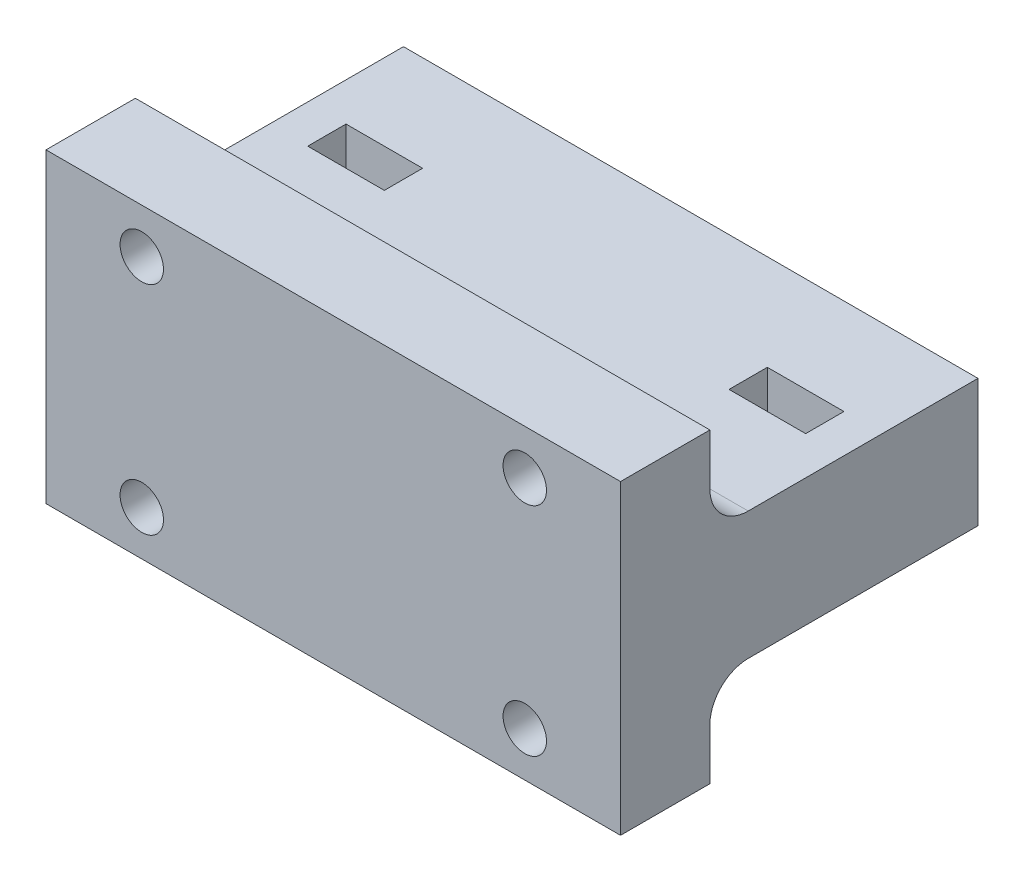
SolidWorks part; units mm, degrees
ref_plane "Спереди" through (0, 0, 0) normal (0, 0, 1) x (1, 0, 0)
ref_plane "Сверху" through (0, 0, 0) normal (0, 1, 0) x (1, 0, 0)
ref_plane "Справа" through (0, 0, 0) normal (1, 0, 0) x (0, 0, -1)
sketch "Эскиз1" plane through (0, 0, 0) normal (0, 0, 1) x (1, 0, 0)
  line L1 (-22.5, 10) -> (22.5, 10)
  line L2 (-22.5, 10) -> (-22.5, -10)
  line L3 (-22.5, -10) -> (22.5, -10)
  line L4 (22.5, 10) -> (22.5, -10)
  line L5 (-22.5, 10) -> (22.5, -10) construction
  line L6 (-22.5, -10) -> (22.5, 10) construction
  point P0 (0, 0)
  dimension "D1" = 45
  dimension "D2" = 20
extrude "Бобышка-Вытянуть1" add sketch "Эскиз1" along normal blind 10
sketch "Эскиз2" plane through (0, 0, 0) normal (0, 0, -1) x (-1, 0, 0)
  line L0 (-22.5, 0) -> (-22.5, 5)
  line L1 (-22.5, -10) -> (-22.5, 10) construction
  line L2 (-22.5, 5) -> (22.5, 5)
  line L3 (22.5, 10) -> (22.5, -10) construction
  line L4 (22.5, 5) -> (22.5, -5)
  line L5 (22.5, -5) -> (-22.5, -5)
  line L6 (-22.5, -5) -> (-22.5, 0)
  dimension "D1" = 10
extrude "Бобышка-Вытянуть2" add sketch "Эскиз2" along normal blind 17
sketch "Эскиз3" plane through (0, 0, 10) normal (0, 0, 1) x (1, 0, 0)
  line L1 (-22.5, 10) -> (-22.5, 12)
  line L2 (-22.5, 12) -> (22.5, 12)
  line L3 (22.5, 12) -> (22.5, 10)
  line L4 (-31.5963, 0) -> (27.5722, 0) construction
  line L5 (22.5, -12) -> (22.5, -10)
  line L6 (-22.5, -12) -> (22.5, -12)
  line L7 (-22.5, -10) -> (-22.5, -12)
  line L8 (-22.5, 10) -> (22.5, 10)
  line L9 (-22.5, -10) -> (22.5, -10)
  line L10 (22.5, -10) -> (22.5, 2.7221)
  line L11 (22.5, -10) -> (22.5, 10) construction
  line M6 (22.5, 10) -> (-22.5, 10)
  line M8 (-22.5, -10) -> (22.5, -10)
  dimension "D1" = 2
extrude "Бобышка-Вытянуть3" add sketch "Эскиз3" against normal blind 10 contours L3 L2 L1 M6 | L7 L6 L5 M8 region at (0, 11, 10) region at (0, -11, 10)
sketch "Эскиз5" plane through (0, 0, 0) normal (0, 0, -1) x (-1, 0, 0)
  line L1 (0, 12) -> (0, 5)
  line L3 (22.5, 12) -> (-22.5, 12) construction
  line L4 (22.5, 5) -> (-22.5, 5) construction
  line L5 (0, 5) -> (0, -5)
  line L6 (-22.5, -5) -> (22.5, -5) construction
  line L7 (0, -5) -> (0, -12)
  line L8 (22.5, -12) -> (-22.5, -12) construction
  line L9 (-22.5, 0) -> (22.5, 0) construction
  line L10 (-22.5, 5) -> (-22.5, -5) construction
  line L11 (22.5, -5) -> (22.5, 5) construction
  line L12 (0, 8.5) -> (-15, 8.5)
  circle A0 centre (-15, 8.5) radius 1.5
  circle A1 centre (15, 8.5) radius 1.5
  circle A2 centre (15, -8.5) radius 1.5
  circle A3 centre (-15, -8.5) radius 1.5
  dimension "D2" = 3
  dimension "D1" = 15
extrude "Вырез-Вытянуть1" cut sketch "Эскиз5" against normal through all contours A1 | A0 | A3 | A2 | A2 | A3 | A1 region at (16.4576, 8.5, 0) region at (-15, 8.5, 0) region at (-15, -8.5, 0) region at (15, -8.5, 0)
sketch "Эскиз8" plane through (0, 0, 0) normal (0, 0, -1) x (-1, 0, 0)
  line L0 (-27.4232, 0) -> (25.3366, 0) construction
  line L1 (-11.8246, 8.5) -> (-13.4123, 11.25)
  line L2 (-13.4123, 11.25) -> (-16.5877, 11.25)
  line L3 (-16.5877, 11.25) -> (-18.1754, 8.5)
  line L4 (-18.1754, 8.5) -> (-16.5877, 5.75)
  line L5 (-16.5877, 5.75) -> (-13.4123, 5.75)
  line L6 (-13.4123, 5.75) -> (-11.8246, 8.5)
  line L7 (0, 16.0589) -> (0, -14.7921) construction
  line L8 (-13.4123, -5.75) -> (-11.8246, -8.5)
  line L9 (-16.5877, -5.75) -> (-13.4123, -5.75)
  line L10 (-18.1754, -8.5) -> (-16.5877, -5.75)
  line L11 (-16.5877, -11.25) -> (-18.1754, -8.5)
  line L12 (-13.4123, -11.25) -> (-16.5877, -11.25)
  line L13 (-11.8246, -8.5) -> (-13.4123, -11.25)
  line L14 (11.8246, -8.5) -> (13.4123, -11.25)
  line L15 (13.4123, -11.25) -> (16.5877, -11.25)
  line L16 (16.5877, -11.25) -> (18.1754, -8.5)
  line L17 (18.1754, -8.5) -> (16.5877, -5.75)
  line L18 (16.5877, -5.75) -> (13.4123, -5.75)
  line L19 (13.4123, -5.75) -> (11.8246, -8.5)
  line L20 (13.4123, 5.75) -> (11.8246, 8.5)
  line L21 (16.5877, 5.75) -> (13.4123, 5.75)
  line L22 (18.1754, 8.5) -> (16.5877, 5.75)
  line L23 (16.5877, 11.25) -> (18.1754, 8.5)
  line L24 (13.4123, 11.25) -> (16.5877, 11.25)
  line L25 (11.8246, 8.5) -> (13.4123, 11.25)
  circle A0 centre (-15, 8.5) radius 2.75 construction
  circle A1 centre (-15, -8.5) radius 2.75 construction
  circle A2 centre (15, -8.5) radius 2.75 construction
  circle A3 centre (15, 8.5) radius 2.75 construction
  dimension "D1" = 5.5
extrude "Вырез-Вытянуть3" cut sketch "Эскиз8" against normal blind 3
fillet "Скругление4" radius 3 1 edges
fillet "Скругление5" radius 3 1 edges
sketch "Эскиз9" plane through (0, 0, 10) normal (0, 0, 1) x (1, 0, 0)
  line L1 (-22.5, 12) -> (22.5, 12)
  line L2 (-22.5, 12) -> (-22.5, -12)
  line L3 (-22.5, -12) -> (22.5, -12)
  line L4 (22.5, 12) -> (22.5, -12)
extrude "Вырез-Вытянуть4" cut sketch "Эскиз9" against normal blind 3
sketch "Эскиз10" plane through (0, 0, -17) normal (0, 0, -1) x (-1, 0, 0)
  line L2 (-22.5, 5) -> (22.5, 5)
  line L3 (-22.5, 5) -> (-22.5, -5)
  line L4 (-22.5, -5) -> (22.5, -5)
  line L5 (22.5, 5) -> (22.5, -5)
extrude "Бобышка-Вытянуть4" add sketch "Эскиз10" along normal blind 3
sketch "Эскиз12" plane through (0, 0, -20) normal (0, 0, -1) x (-1, 0, 0)
  line L0 (-22.5, 0) -> (-16.5, 0)
  line L1 (-22.5, 5) -> (-22.5, -5) construction
  line L2 (0, 5) -> (0, -5)
  line L3 (22.5, 5) -> (-22.5, 5) construction
  line L4 (-22.5, -5) -> (22.5, -5) construction
  circle A0 centre (-16.5, 0) radius 1.55
  circle A1 centre (16.5, 0) radius 1.55
  dimension "D2" = 3.1
  dimension "D1" = 6
extrude "Вырез-Вытянуть5" cut sketch "Эскиз12" against normal blind 15 contours A0 | A1 region at (16.5, -1.5062, -20) region at (-16.5, 0, -20)
sketch "Эскиз13" plane through (0, 5, 0) normal (0, 1, 0) x (1, 0, 0)
  line L0 (22.5, 12) -> (16.5, 12)
  line L1 (16.5, 12) -> (16.5, 13.5)
  line L2 (22.5, 20) -> (22.5, 3) construction
  line L3 (22.5, 20) -> (22.5, 12)
  line L4 (16.5, 13.5) -> (13.5, 13.5)
  line L5 (13.5, 13.5) -> (13.5, 10.5)
  line L6 (13.5, 10.5) -> (19.5, 10.5)
  line L7 (19.5, 10.5) -> (19.5, 13.5)
  line L8 (19.5, 13.5) -> (16.5, 13.5)
  line L9 (0, 20) -> (0, 3)
  line L10 (-22.5, 20) -> (22.5, 20) construction
  line L11 (-22.5, 3) -> (22.5, 3) construction
  line L12 (-19.5, 13.5) -> (-16.5, 13.5)
  line L13 (-19.5, 10.5) -> (-19.5, 13.5)
  line L14 (-13.5, 10.5) -> (-19.5, 10.5)
  line L15 (-13.5, 13.5) -> (-13.5, 10.5)
  line L16 (-16.5, 13.5) -> (-13.5, 13.5)
  line L17 (-16.5, 12) -> (-16.5, 13.5)
  dimension "D1" = 6
  dimension "D2" = 8
  dimension "D3" = 1.5
  dimension "D4" = 3
  dimension "D5" = 3
extrude "Вырез-Вытянуть6" cut sketch "Эскиз13" against normal blind 8 contours L6 L7 L0 L1 L4 L5 | L7 L8 L1 L0 | L16 L12 L13 L14 L15 region at (16, 5, -11.75) region at (18, 5, -12.75) region at (-18, 5, -13.4329)
sketch "Эскиз15" plane through (0, 0, -20) normal (0, 0, -1) x (-1, 0, 0)
  line L1 (-22.5, 5) -> (22.5, 5)
  line L2 (-22.5, 5) -> (-22.5, -5)
  line L3 (-22.5, -5) -> (22.5, -5)
  line L4 (22.5, 5) -> (22.5, -5)
  circle A0 centre (-16.5, 0) radius 1.55
  circle A1 centre (16.5, 0) radius 1.55
extrude "Бобышка-Вытянуть5" add sketch "Эскиз15" along normal blind 1
sketch "Эскиз16" plane through (0, 0, 7) normal (0, 0, 1) x (1, 0, 0)
  circle A0 centre (15, -8.5) radius 1.7
  circle A1 centre (-15, -8.5) radius 1.7
  circle A2 centre (-15, 8.5) radius 1.7
  circle A3 centre (15, 8.5) radius 1.7
  dimension "D1" = 3.4
extrude "Вырез-Вытянуть7" cut sketch "Эскиз16" against normal through all
sketch "Эскиз17" plane through (0, 0, -21) normal (0, 0, -1) x (-1, 0, 0)
  line L1 (-13.2968, 5.55) -> (-11.5936, 8.5)
  line L2 (-11.5936, 8.5) -> (-13.2968, 11.45)
  line L3 (-13.2968, 11.45) -> (-16.7032, 11.45)
  line L4 (-16.7032, 11.45) -> (-18.4064, 8.5)
  line L5 (-18.4064, 8.5) -> (-16.7032, 5.55)
  line L6 (-16.7032, 5.55) -> (-13.2968, 5.55)
  line L7 (16.7032, 5.55) -> (18.4064, 8.5)
  line L8 (18.4064, 8.5) -> (16.7032, 11.45)
  line L9 (16.7032, 11.45) -> (13.2968, 11.45)
  line L10 (13.2968, 11.45) -> (11.5936, 8.5)
  line L11 (11.5936, 8.5) -> (13.2968, 5.55)
  line L12 (13.2968, 5.55) -> (16.7032, 5.55)
  line L13 (16.7032, -11.45) -> (18.4064, -8.5)
  line L14 (18.4064, -8.5) -> (16.7032, -5.55)
  line L15 (16.7032, -5.55) -> (13.2968, -5.55)
  line L16 (13.2968, -5.55) -> (11.5936, -8.5)
  line L17 (11.5936, -8.5) -> (13.2968, -11.45)
  line L18 (13.2968, -11.45) -> (16.7032, -11.45)
  line L19 (-13.2968, -11.45) -> (-11.5936, -8.5)
  line L20 (-11.5936, -8.5) -> (-13.2968, -5.55)
  line L21 (-13.2968, -5.55) -> (-16.7032, -5.55)
  line L22 (-16.7032, -5.55) -> (-18.4064, -8.5)
  line L23 (-18.4064, -8.5) -> (-16.7032, -11.45)
  line L24 (-16.7032, -11.45) -> (-13.2968, -11.45)
  circle A0 centre (-15, 8.5) radius 2.95 construction
  circle A1 centre (15, 8.5) radius 2.95 construction
  circle A2 centre (15, -8.5) radius 2.95 construction
  circle A3 centre (-15, -8.5) radius 2.95 construction
  dimension "D1" = 5.9
  dimension "D2" = 5.9
  dimension "D3" = 5.9
  dimension "D4" = 5.9
extrude "Вырез-Вытянуть8" cut sketch "Эскиз17" against normal up to surface (24 mm away) up to face at (16.7, -8.5, 3)
sketch "Эскиз18" plane through (0, 0, -21) normal (0, 0, -1) x (-1, 0, 0)
  circle A0 centre (-16.5, 0) radius 1.7
  circle A1 centre (16.5, 0) radius 1.7
  dimension "D1" = 3.4
extrude "Вырез-Вытянуть9" cut sketch "Эскиз18" against normal up to surface (16 mm away) up to face at (14.95, 0, -5)
